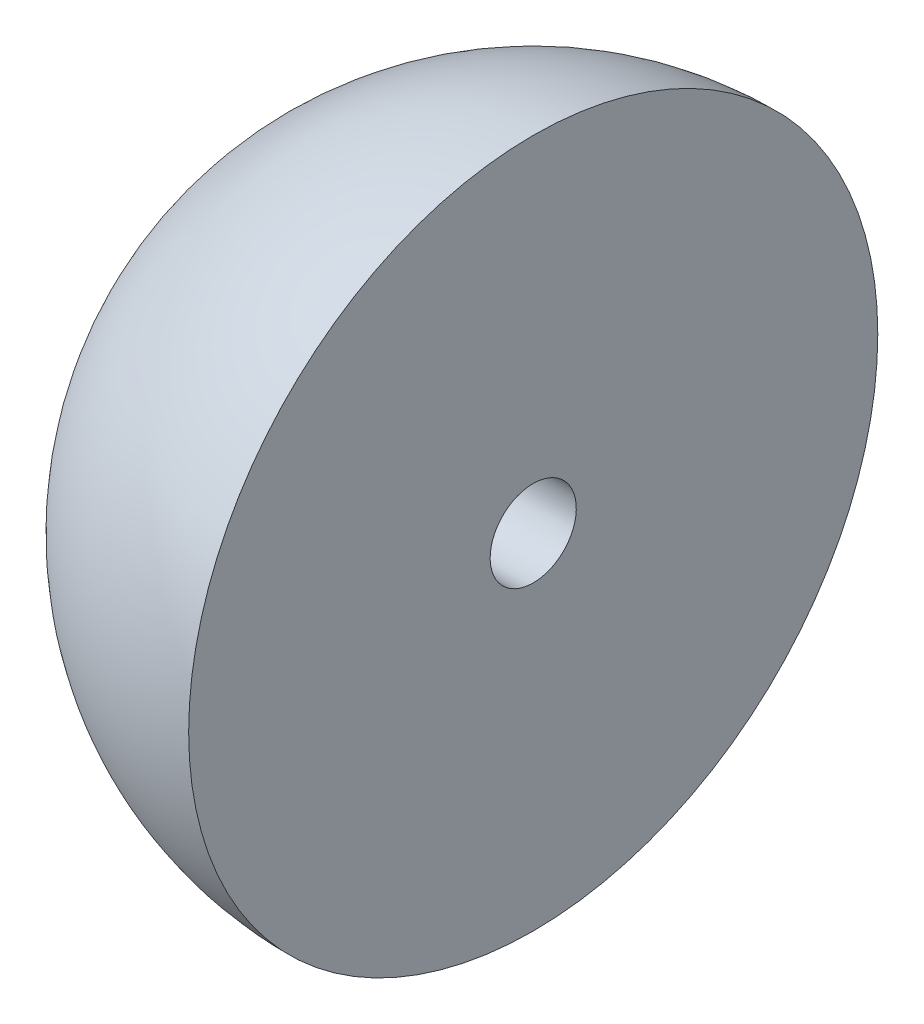
SolidWorks part; units mm, degrees
ref_plane "Front Plane" through (0, 0, 0) normal (0, 0, 1) x (1, 0, 0)
ref_plane "Top Plane" through (0, 0, 0) normal (0, 1, 0) x (1, 0, 0)
ref_plane "Right Plane" through (0, 0, 0) normal (1, 0, 0) x (0, 0, -1)
sketch "Sketch1" plane through (0, 0, 0) normal (1, 0, 0) x (0, 0, -1)
  line L0 (-18, 0) -> (18, 0)
  arc A0 (-18, 0) -> (18, 0) centre (0, 0) ccw
  dimension "D1" = 18
revolve "Revolve1" add sketch "Sketch1" angle 180 about L0
sketch "Sketch2" plane through (0, 0, 0) normal (1, 0, 0) x (0, 0, -1)
  circle A0 centre (0, 0) radius 2.25
  dimension "D1" = 4.5
extrude "Cut-Extrude1" cut sketch "Sketch2" against normal blind 15
sketch "Sketch4" plane through (0, 0, 0) normal (0, 1, 0) x (1, 0, 0)
  line L1 (-5.6418, -3.5) -> (-8.6418, -3.5)
  line L2 (-5.6418, -3.5) -> (-5.6418, 3.5)
  line L3 (-5.6418, 3.5) -> (-8.6418, 3.5)
  line L4 (-8.6418, -3.5) -> (-8.6418, 3.5)
  point P4 (-5.6418, 0)
  dimension "D1" = 7
  dimension "D2" = 3
extrude "Cut-Extrude2" cut sketch "Sketch4" against normal through all and the other way blind 5
